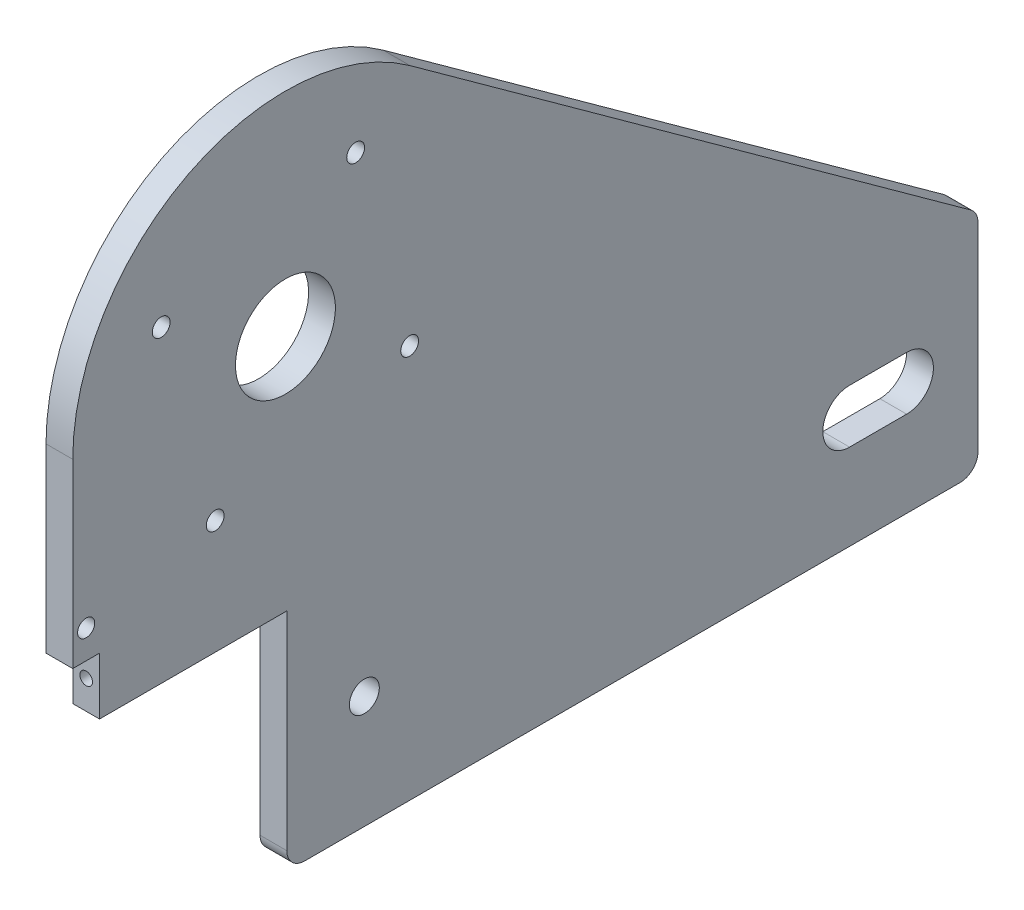
SolidWorks part; units mm, degrees
ref_plane "Front Plane" through (0, 0, 0) normal (0, 0, 1) x (1, 0, 0)
ref_plane "Top Plane" through (0, 0, 0) normal (0, 1, 0) x (1, 0, 0)
ref_plane "Right Plane" through (0, 0, 0) normal (1, 0, 0) x (0, 0, -1)
sketch "Sketch1" plane through (0, 0, 0) normal (1, 0, 0) x (0, 0, -1)
  line L0 (-39.2828, 0) -> (77.3828, 0)
  line L1 (80.5578, 3.175) -> (80.5578, 38.5097)
  line L2 (-80.5578, 82.55) -> (-80.5578, 50.292)
  line L3 (79.2431, 41.0826) -> (-20.5306, 113.2224)
  line L4 (-75.7953, 50.292) -> (-75.7953, 40.132)
  line L5 (-80.5578, 50.292) -> (-75.7953, 50.292)
  line L6 (67.8578, 20.066) -> (57.6978, 20.066) construction
  line L7 (-75.7953, 40.132) -> (-42.4578, 40.132)
  line L10 (-42.4578, 40.132) -> (-42.4578, 3.175)
  line L11 (-38.3203, 96.7465) -> (80.2327, 60.1074) construction
  line L12 (-52.6061, 71.4678) -> (39.9396, -11.1914) construction
  line L13 (67.8578, 15.3035) -> (57.6978, 15.3035)
  line L14 (67.8578, 24.8285) -> (57.6978, 24.8285)
  arc A0 (67.8578, 15.3035) -> (67.8578, 24.8285) centre (67.8578, 20.066) ccw
  circle A1 centre (-42.7078, 82.55) radius 31.5 construction
  circle A2 centre (67.8578, 20.066) radius 76.2 construction
  circle A3 centre (67.8578, 20.066) radius 41.91 construction
  circle A4 centre (-42.7078, 82.55) radius 14.859 construction
  arc A5 (-20.5306, 113.2224) -> (-80.5578, 82.55) centre (-42.7078, 82.55) ccw
  arc A6 (-39.2828, 0) -> (-42.4578, 3.175) centre (-39.2828, 3.175) cw
  arc A7 (77.3828, 0) -> (80.5578, 3.175) centre (77.3828, 3.175) ccw
  arc A8 (80.5578, 38.5097) -> (79.2431, 41.0826) centre (77.3828, 38.5097) ccw
  circle A10 centre (-55.209, 60.4394) radius 1.5875
  circle A11 centre (-28.6622, 20.066) radius 2.667
  circle A12 centre (-20.5972, 70.0488) radius 1.5875
  circle A13 centre (-64.8184, 95.0512) radius 1.5875
  circle A14 centre (-30.2065, 104.6606) radius 1.5875
  circle A15 centre (-78.1765, 55.372) radius 1.524
  circle A16 centre (-42.7078, 82.55) radius 8.89
  arc A17 (57.6978, 24.8285) -> (57.6978, 15.3035) centre (57.6978, 20.066) ccw
  point P28 (80.5578, 40.132)
  point P39 (62.7778, 20.066)
  dimension "D4" = 9.525
  dimension "D7" = 29.718
  dimension "D8" = 63
  dimension "D9" = 6.35
  dimension "D12" = 3.175
  dimension "D14" = 83.82
  dimension "D15" = 152.4
  dimension "D18" = 5.334
  dimension "D19" = 3.175
  dimension "D23" = 3.048
  dimension "D2" = 40.132
  dimension "D3" = 20.066
  dimension "D5" = 12.7
  dimension "D6" = 33.3375
  dimension "D10" = 127
  dimension "D11" = 109.22
  dimension "D17" = 25.4
  dimension "D21" = 4.7625
  dimension "D22" = 10.16
  dimension "D24" = 5.08
  dimension "D25" = 2.3813
  dimension "D26" = 10.16
  dimension "D16" = 4
extrude "Boss-Extrude1" add sketch "Sketch1" along normal blind 4.7625
sketch "Sketch2" plane through (0, 0, 75.7953) normal (0, 0, 1) x (1, 0, 0)
  line L0 (4.7625, 50.292) -> (4.7625, 40.132) construction
  line L1 (4.7625, 40.132) -> (0, 40.132) construction
  circle A0 centre (2.3813, 45.212) radius 1.1303
  point P4 (4.7625, 45.212)
  point P7 (2.3813, 40.132)
  dimension "D1" = 2.2606
extrude "Cut-Extrude1" cut sketch "Sketch2" against normal blind 6.35
